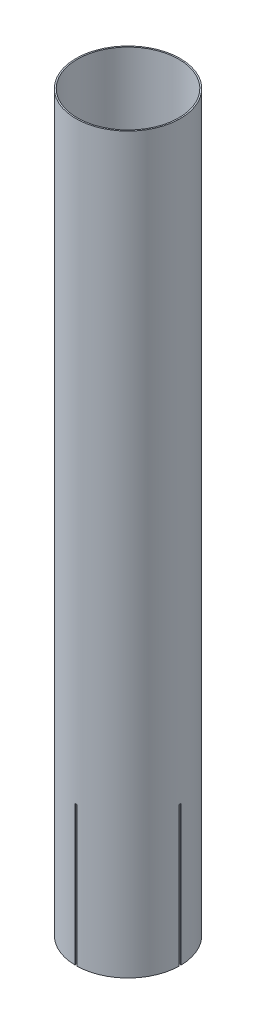
SolidWorks part; units mm, degrees
material "Thornel Mat VMA"
ref_plane "Front Plane" through (0, 0, 0) normal (0, 0, 1) x (1, 0, 0)
ref_plane "Top Plane" through (0, 0, 0) normal (0, 1, 0) x (1, 0, 0)
ref_plane "Right Plane" through (0, 0, 0) normal (1, 0, 0) x (0, 0, -1)
sketch "Sketch1" plane through (0, 0, 0) normal (0, 0, 1) x (1, 0, 0)
  line L0 (78.2, 0) -> (78.2, 1100)
  line L1 (0, 0) -> (0, 2000) construction
  line L9 (76.2, 0) -> (76.2, 1100)
  line L10 (78.2, 0) -> (76.2, 0)
  line L11 (78.2, 1100) -> (76.2, 1100)
  point P7 (65, 1600)
  point P8 (-1029.1667, 1600)
  point P9 (-9.3208, 1996.3774)
  dimension "D1" = 1100
  dimension "D2" = 76.2
  dimension "D3" = 2000
  dimension "D4" = 2
revolve "Revolve1" add sketch "Sketch1" angle 360 about L1
sketch "Sketch2" plane through (0, 0, 0) normal (0, 0, 1) x (1, 0, 0)
  line L0 (-185.2, 150) -> (-185.2, 0)
  line L1 (-185.2, 0) -> (-78.2, 0)
  line L2 (-78.2, 0) -> (-78.2, 210) construction
  line L3 (-78.2, 210) -> (-185.2, 150)
  line L4 (-78.2, 0) -> (0, 0)
  line L5 (-78.2, 210) -> (0, 210)
  line L6 (0, 0) -> (0, 210)
  dimension "D1" = 210
  dimension "D2" = 150
  dimension "D3" = 107
extrude "Cut-Extrude1" cut sketch "Sketch2" against normal blind 1.5 and the other way blind 1.5
pattern_circular "CirPattern1" count 4 over 360 about axis through (0, 0, 0) along (0, -1, 0) of "Cut-Extrude1"
